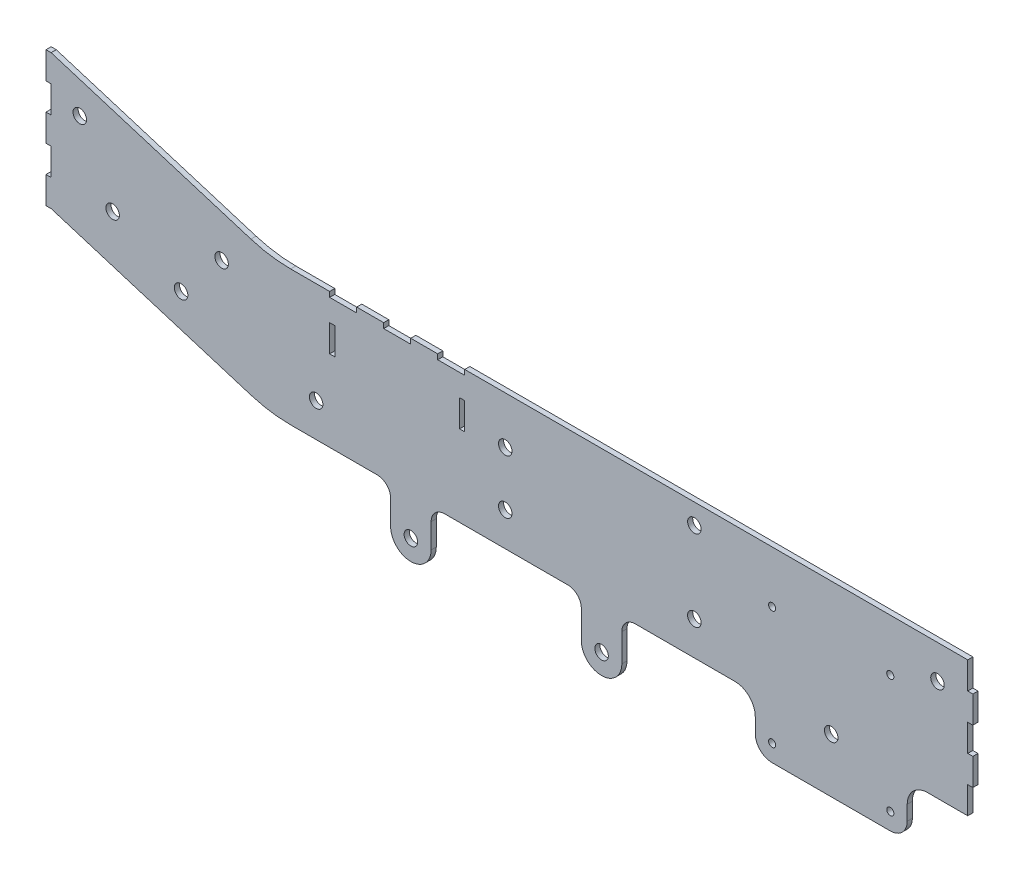
SolidWorks part; units mm, degrees
material "1060 Alloy"
ref_plane "Front Plane" through (0, 0, 0) normal (0, 0, 1) x (1, 0, 0)
ref_plane "Top Plane" through (0, 0, 0) normal (0, 1, 0) x (1, 0, 0)
ref_plane "Right Plane" through (0, 0, 0) normal (1, 0, 0) x (0, 0, -1)
sketch "Sketch2" plane through (0, 0, 0) normal (0, 0, 1) x (1, 0, 0)
  line L41 (-214.6997, -160.1998) -> (-26.8739, -218.0697)
  line L42 (10.5206, -223.6998) -> (91.8093, -223.6998)
  line L43 (104.5093, -236.3998) -> (104.5093, -259.4448)
  line L44 (142.6093, -259.4448) -> (142.6093, -236.3998)
  line L45 (155.3093, -223.6998) -> (271.0993, -223.6998)
  line L46 (283.7993, -236.3998) -> (283.7993, -262.6248)
  line L47 (321.8993, -262.6248) -> (321.8993, -236.3998)
  line L48 (334.5993, -223.6998) -> (476.2017, -223.6998)
  line L49 (561.2969, -223.6998) -> (656.7743, -223.6998)
  line L50 (656.7743, -223.6998) -> (656.7743, -198.2998)
  line L51 (656.7743, -198.2998) -> (651.9483, -198.2998)
  line L52 (651.9483, -198.2998) -> (651.9483, -172.8998)
  line L53 (651.9483, -172.8998) -> (656.7743, -172.8998)
  line L54 (656.7743, -172.8998) -> (656.7743, -147.4998)
  line L55 (656.7743, -147.4998) -> (651.9483, -147.4998)
  line L56 (651.9483, -147.4998) -> (651.9483, -122.0998)
  line L57 (651.9483, -122.0998) -> (656.7743, -122.0998)
  line L58 (656.7743, -122.0998) -> (656.7743, -96.6998)
  line L59 (656.7743, -96.6998) -> (174.1743, -96.6998)
  line L60 (174.1743, -96.6998) -> (174.1743, -101.5258)
  line L61 (174.1743, -101.5258) -> (148.7743, -101.5258)
  line L62 (148.7743, -101.5258) -> (148.7743, -96.6998)
  line L63 (148.7743, -96.6998) -> (123.3743, -96.6998)
  line L64 (123.3743, -96.6998) -> (123.3743, -101.5258)
  line L65 (123.3743, -101.5258) -> (97.9743, -101.5258)
  line L66 (97.9743, -101.5258) -> (97.9743, -96.6998)
  line L67 (97.9743, -96.6998) -> (72.5743, -96.6998)
  line L68 (72.5743, -96.6998) -> (72.5743, -101.5258)
  line L69 (72.5743, -101.5258) -> (47.1743, -101.5258)
  line L70 (47.1743, -101.5258) -> (47.1743, -96.6998)
  line L71 (47.1743, -96.6998) -> (10.5206, -96.6998)
  line L72 (-214.6997, -160.1998) -> (-26.8739, -218.0697)
  line L73 (-219.5257, -33.1998) -> (-219.5257, -58.5998)
  line L74 (-219.5257, -58.5998) -> (-214.6997, -58.5998)
  line L75 (-214.6997, -58.5998) -> (-214.6997, -83.9998)
  line L76 (-214.6997, -83.9998) -> (-219.5257, -83.9998)
  line L77 (-219.5257, -83.9998) -> (-219.5257, -109.3998)
  line L78 (-219.5257, -109.3998) -> (-214.6997, -109.3998)
  line L79 (-214.6997, -109.3998) -> (-214.6997, -134.7998)
  line L80 (-214.6997, -134.7998) -> (-219.5257, -134.7998)
  line L81 (-219.5257, -134.7998) -> (-219.5257, -160.1998)
  line L82 (-26.8739, -91.0697) -> (-214.6997, -33.1998)
  line L83 (10.5206, -223.6998) -> (91.8093, -223.6998)
  line L84 (104.5093, -236.3998) -> (104.5093, -259.4448)
  line L85 (142.6093, -259.4448) -> (142.6093, -236.3998)
  line L86 (155.3093, -223.6998) -> (271.0993, -223.6998)
  line L87 (283.7993, -236.3998) -> (283.7993, -262.6248)
  line L88 (321.8993, -262.6248) -> (321.8993, -236.3998)
  line L89 (334.5993, -223.6998) -> (476.2017, -223.6998)
  line L90 (561.2969, -223.6998) -> (656.7743, -223.6998)
  line L91 (656.7743, -223.6998) -> (656.7743, -198.2998)
  line L92 (656.7743, -198.2998) -> (651.9483, -198.2998)
  line L93 (651.9483, -198.2998) -> (651.9483, -172.8998)
  line L94 (651.9483, -172.8998) -> (656.7743, -172.8998)
  line L95 (656.7743, -172.8998) -> (656.7743, -147.4998)
  line L96 (656.7743, -147.4998) -> (651.9483, -147.4998)
  line L97 (651.9483, -147.4998) -> (651.9483, -122.0998)
  line L98 (651.9483, -122.0998) -> (656.7743, -122.0998)
  line L99 (656.7743, -122.0998) -> (656.7743, -96.6998)
  line L100 (656.7743, -96.6998) -> (174.1743, -96.6998)
  line L101 (174.1743, -96.6998) -> (174.1743, -101.5258)
  line L102 (174.1743, -101.5258) -> (148.7743, -101.5258)
  line L103 (148.7743, -101.5258) -> (148.7743, -96.6998)
  line L104 (148.7743, -96.6998) -> (123.3743, -96.6998)
  line L105 (123.3743, -96.6998) -> (123.3743, -101.5258)
  line L106 (123.3743, -101.5258) -> (97.9743, -101.5258)
  line L107 (97.9743, -101.5258) -> (97.9743, -96.6998)
  line L108 (97.9743, -96.6998) -> (72.5743, -96.6998)
  line L109 (72.5743, -96.6998) -> (72.5743, -101.5258)
  line L110 (72.5743, -101.5258) -> (47.1743, -101.5258)
  line L111 (47.1743, -101.5258) -> (47.1743, -96.6998)
  line L112 (47.1743, -96.6998) -> (10.5206, -96.6998)
  line L113 (-26.8739, -91.0697) -> (-214.6997, -33.1998)
  line L114 (-219.5257, -33.1998) -> (-219.5257, -58.5998)
  line L115 (-219.5257, -58.5998) -> (-214.6997, -58.5998)
  line L116 (-214.6997, -58.5998) -> (-214.6997, -83.9998)
  line L117 (-214.6997, -83.9998) -> (-219.5257, -83.9998)
  line L118 (-219.5257, -83.9998) -> (-219.5257, -109.3998)
  line L119 (-219.5257, -109.3998) -> (-214.6997, -109.3998)
  line L120 (-214.6997, -109.3998) -> (-214.6997, -134.7998)
  line L121 (-214.6997, -134.7998) -> (-219.5257, -134.7998)
  line L122 (-219.5257, -134.7998) -> (-219.5257, -160.1998)
  line L412 (-214.6997, -33.1998) -> (-219.5257, -33.1998)
  line L413 (-214.6997, -33.1998) -> (-219.5257, -33.1998)
  line L414 (-219.5257, -160.1998) -> (-214.6997, -160.1998)
  line L415 (-219.5257, -160.1998) -> (-214.6997, -160.1998)
  arc A11 (-26.8739, -218.0697) -> (10.5206, -223.6998) centre (10.5206, -96.6998) ccw
  arc A12 (104.5093, -236.3998) -> (91.8093, -223.6998) centre (91.8093, -236.3998) ccw
  arc A13 (104.5093, -259.4448) -> (142.6093, -259.4448) centre (123.5593, -259.4448) ccw
  arc A14 (155.3093, -223.6998) -> (142.6093, -236.3998) centre (155.3093, -236.3998) ccw
  arc A15 (283.7993, -236.3998) -> (271.0993, -223.6998) centre (271.0993, -236.3998) ccw
  arc A16 (283.7993, -262.6248) -> (321.8993, -262.6248) centre (302.8493, -262.6248) ccw
  arc A17 (334.5993, -223.6998) -> (321.8993, -236.3998) centre (334.5993, -236.3998) ccw
  arc A18 (486.8386, -229.461) -> (476.2017, -223.6998) centre (476.2017, -236.3998) ccw
  arc A19 (486.8386, -229.461) -> (550.66, -229.461) centre (518.7493, -208.6448) ccw
  arc A20 (561.2969, -223.6998) -> (550.66, -229.461) centre (561.2969, -236.3998) ccw
  arc A21 (-26.8739, -218.0697) -> (10.5206, -223.6998) centre (10.5206, -96.6998) ccw
  arc A22 (-26.8739, -91.0697) -> (10.5206, -96.6998) centre (10.5206, 30.3002) ccw
  arc A23 (104.5093, -236.3998) -> (91.8093, -223.6998) centre (91.8093, -236.3998) ccw
  arc A24 (104.5093, -259.4448) -> (142.6093, -259.4448) centre (123.5593, -259.4448) ccw
  arc A25 (155.3093, -223.6998) -> (142.6093, -236.3998) centre (155.3093, -236.3998) ccw
  arc A26 (283.7993, -236.3998) -> (271.0993, -223.6998) centre (271.0993, -236.3998) ccw
  arc A27 (283.7993, -262.6248) -> (321.8993, -262.6248) centre (302.8493, -262.6248) ccw
  arc A28 (334.5993, -223.6998) -> (321.8993, -236.3998) centre (334.5993, -236.3998) ccw
  arc A29 (486.8386, -229.461) -> (476.2017, -223.6998) centre (476.2017, -236.3998) ccw
  arc A30 (486.8386, -229.461) -> (550.66, -229.461) centre (518.7493, -208.6448) ccw
  arc A31 (561.2969, -223.6998) -> (550.66, -229.461) centre (561.2969, -236.3998) ccw
  arc A32 (-26.8739, -91.0697) -> (10.5206, -96.6998) centre (10.5206, 30.3002) ccw
  circle A56 centre (390.0743, -191.9498) radius 6.35
  circle A57 centre (390.0743, -191.9498) radius 6.35
  circle A58 centre (390.0743, -115.7498) radius 6.35
  circle A59 centre (390.0743, -115.7498) radius 6.35
  circle A60 centre (518.7493, -221.3448) radius 6.35
  circle A61 centre (518.7493, -221.3448) radius 6.35
  circle A62 centre (618.6743, -128.4498) radius 6.35
  circle A63 centre (618.6743, -128.4498) radius 6.35
  circle A64 centre (302.8493, -262.6248) radius 6.35
  circle A65 centre (302.8493, -262.6248) radius 6.35
  circle A66 centre (212.2743, -191.9498) radius 6.35
  circle A67 centre (212.2743, -191.9498) radius 6.35
  circle A68 centre (212.2743, -141.1498) radius 6.35
  circle A69 centre (212.2743, -141.1498) radius 6.35
  circle A70 centre (123.5593, -259.4448) radius 6.35
  circle A71 centre (123.5593, -259.4448) radius 6.35
  circle A72 centre (34.4743, -191.9498) radius 6.35
  circle A73 centre (34.4743, -191.9498) radius 6.35
  circle A74 centre (-92.5257, -166.5498) radius 6.35
  circle A75 centre (-92.5257, -166.5498) radius 6.35
  circle A76 centre (-156.8507, -133.7248) radius 6.35
  circle A77 centre (-156.8507, -133.7248) radius 6.35
  circle A78 centre (-54.4257, -122.0998) radius 6.35
  circle A79 centre (-54.4257, -122.0998) radius 6.35
  circle A80 centre (-187.7757, -71.2998) radius 6.35
  circle A81 centre (-187.7757, -71.2998) radius 6.35
  dimension "D1" = 0
  dimension "D2" = 0
  dimension "D3" = 0
  dimension "D4" = 0
  dimension "D5" = 0
  dimension "D6" = 0
  dimension "D7" = 0
  dimension "D8" = 0
  dimension "D9" = 0
  dimension "D10" = 0
  dimension "D11" = 0
  dimension "D12" = 0
  dimension "D13" = 0
  dimension "D14" = 0
extrude "base" add sketch "Sketch2" along normal blind 4.826
sketch "Sketch3" plane through (0, 0, 4.826) normal (0, 0, 1) x (1, 0, 0)
  line L0 (47.1743, -101.5258) -> (47.1743, -96.6998) construction
  line L1 (169.3483, -122.0998) -> (174.1743, -122.0998)
  line L2 (169.3483, -122.0998) -> (169.3483, -147.4998)
  line L3 (169.3483, -147.4998) -> (174.1743, -147.4998)
  line L4 (174.1743, -122.0998) -> (174.1743, -147.4998)
  line L5 (47.1743, -122.0998) -> (52.0003, -122.0998)
  line L6 (47.1743, -122.0998) -> (47.1743, -147.4998)
  line L7 (47.1743, -147.4998) -> (52.0003, -147.4998)
  line L8 (52.0003, -122.0998) -> (52.0003, -147.4998)
  line L9 (174.1743, -96.6998) -> (174.1743, -101.5258) construction
  line L10 (97.9743, -96.6998) -> (72.5743, -96.6998) construction
  dimension "D1" = 4.826
  dimension "D2" = 25.4
  dimension "D3" = 25.4
extrude "center support vertical holes" cut sketch "Sketch3" against normal through all
sketch "Sketch4" plane through (656.7743, 0, 0) normal (1, 0, 0) x (0, 0, -1)
  line L0 (0, -122.0998) -> (0, -96.6998) construction
  line L1 (0, -96.6998) -> (-4.826, -96.6998) construction
  line L2 (-4.826, -96.6998) -> (-4.826, -122.0998) construction
  line L3 (-4.826, -122.0998) -> (0, -122.0998) construction
  line L4 (0, -172.8998) -> (0, -147.4998) construction
  line L5 (0, -147.4998) -> (-4.826, -147.4998) construction
  line L6 (-4.826, -147.4998) -> (-4.826, -172.8998) construction
  line L7 (-4.826, -172.8998) -> (0, -172.8998) construction
  line L8 (0, -223.6998) -> (0, -198.2998) construction
  line L9 (0, -198.2998) -> (-4.826, -198.2998) construction
  line L10 (-4.826, -198.2998) -> (-4.826, -223.6998) construction
  line L11 (-4.826, -223.6998) -> (0, -223.6998) construction
  line L12 (0, -122.0998) -> (0, -96.6998)
  line L13 (0, -96.6998) -> (-4.826, -96.6998)
  line L14 (-4.826, -96.6998) -> (-4.826, -122.0998)
  line L15 (-4.826, -122.0998) -> (0, -122.0998)
  line L16 (0, -172.8998) -> (0, -147.4998)
  line L17 (0, -147.4998) -> (-4.826, -147.4998)
  line L18 (-4.826, -147.4998) -> (-4.826, -172.8998)
  line L19 (-4.826, -172.8998) -> (0, -172.8998)
  line L20 (0, -223.6998) -> (0, -198.2998)
  line L21 (0, -198.2998) -> (-4.826, -198.2998)
  line L22 (-4.826, -198.2998) -> (-4.826, -223.6998)
  line L23 (-4.826, -223.6998) -> (0, -223.6998)
extrude "Cut-Extrude2" cut sketch "Sketch4" against normal blind 9.652
sketch "Sketch5" plane through (0, 0, 0) normal (0, 0, 1) x (1, 0, 0)
  line L0 (463.2122, -272.4369) -> (574.3372, -272.4369)
  line L1 (447.3372, -256.5619) -> (447.3372, -242.7498)
  line L3 (590.2122, -256.5619) -> (590.2122, -242.7498)
  line L43 (647.1223, -198.2998) -> (651.9483, -198.2998)
  line L44 (651.9483, -198.2998) -> (651.9483, -172.8998)
  line L45 (651.9483, -172.8998) -> (647.1223, -172.8998)
  line L46 (647.1223, -172.8998) -> (647.1223, -147.4998)
  line L47 (647.1223, -147.4998) -> (651.9483, -147.4998)
  line L48 (651.9483, -147.4998) -> (651.9483, -122.0998)
  line L49 (651.9483, -122.0998) -> (647.1223, -122.0998)
  line L50 (647.1223, -122.0998) -> (647.1223, -96.6998)
  line L51 (647.1223, -96.6998) -> (174.1743, -96.6998)
  line L52 (174.1743, -96.6998) -> (174.1743, -101.5258)
  line L53 (174.1743, -101.5258) -> (148.7743, -101.5258)
  line L54 (148.7743, -101.5258) -> (148.7743, -96.6998)
  line L55 (148.7743, -96.6998) -> (123.3743, -96.6998)
  line L56 (123.3743, -96.6998) -> (123.3743, -101.5258)
  line L57 (123.3743, -101.5258) -> (97.9743, -101.5258)
  line L58 (97.9743, -101.5258) -> (97.9743, -96.6998)
  line L59 (97.9743, -96.6998) -> (72.5743, -96.6998)
  line L60 (72.5743, -96.6998) -> (72.5743, -101.5258)
  line L61 (72.5743, -101.5258) -> (47.1743, -101.5258)
  line L62 (47.1743, -101.5258) -> (47.1743, -96.6998)
  line L63 (47.1743, -96.6998) -> (10.5206, -96.6998)
  line L64 (-26.8739, -91.0697) -> (-214.6997, -33.1998)
  line L65 (-214.6997, -33.1998) -> (-219.5257, -33.1998)
  line L66 (-219.5257, -33.1998) -> (-219.5257, -58.5998)
  line L67 (-219.5257, -58.5998) -> (-214.6997, -58.5998)
  line L68 (-214.6997, -58.5998) -> (-214.6997, -83.9998)
  line L69 (-214.6997, -83.9998) -> (-219.5257, -83.9998)
  line L70 (-219.5257, -83.9998) -> (-219.5257, -109.3998)
  line L71 (-219.5257, -109.3998) -> (-214.6997, -109.3998)
  line L72 (-214.6997, -109.3998) -> (-214.6997, -134.7998)
  line L73 (-214.6997, -134.7998) -> (-219.5257, -134.7998)
  line L74 (-219.5257, -134.7998) -> (-219.5257, -160.1998)
  line L75 (-219.5257, -160.1998) -> (-214.6997, -160.1998)
  line L76 (-214.6997, -160.1998) -> (-26.8739, -218.0697)
  line L77 (10.5206, -223.6998) -> (91.8093, -223.6998)
  line L78 (104.5093, -236.3998) -> (104.5093, -259.4448)
  line L79 (142.6093, -259.4448) -> (142.6093, -236.3998)
  line L80 (155.3093, -223.6998) -> (271.0993, -223.6998)
  line L81 (283.7993, -236.3998) -> (283.7993, -262.6248)
  line L82 (321.8993, -262.6248) -> (321.8993, -236.3998)
  line L83 (334.5993, -223.6998) -> (476.2017, -223.6998)
  line L84 (561.2969, -223.6998) -> (647.1223, -223.6998)
  line L85 (647.1223, -223.6998) -> (647.1223, -198.2998)
  line L86 (647.1223, -198.2998) -> (651.9483, -198.2998)
  line L87 (651.9483, -198.2998) -> (651.9483, -172.8998)
  line L88 (651.9483, -172.8998) -> (647.1223, -172.8998)
  line L89 (647.1223, -172.8998) -> (647.1223, -147.4998)
  line L90 (647.1223, -147.4998) -> (651.9483, -147.4998)
  line L91 (651.9483, -147.4998) -> (651.9483, -122.0998)
  line L92 (651.9483, -122.0998) -> (647.1223, -122.0998)
  line L93 (647.1223, -122.0998) -> (647.1223, -96.6998)
  line L94 (647.1223, -96.6998) -> (174.1743, -96.6998)
  line L95 (174.1743, -96.6998) -> (174.1743, -101.5258)
  line L96 (174.1743, -101.5258) -> (148.7743, -101.5258)
  line L97 (148.7743, -101.5258) -> (148.7743, -96.6998)
  line L98 (148.7743, -96.6998) -> (123.3743, -96.6998)
  line L99 (123.3743, -96.6998) -> (123.3743, -101.5258)
  line L100 (123.3743, -101.5258) -> (97.9743, -101.5258)
  line L101 (97.9743, -101.5258) -> (97.9743, -96.6998)
  line L102 (97.9743, -96.6998) -> (72.5743, -96.6998)
  line L103 (72.5743, -96.6998) -> (72.5743, -101.5258)
  line L104 (72.5743, -101.5258) -> (47.1743, -101.5258)
  line L105 (47.1743, -101.5258) -> (47.1743, -96.6998)
  line L106 (47.1743, -96.6998) -> (10.5206, -96.6998)
  line L107 (-26.8739, -91.0697) -> (-214.6997, -33.1998)
  line L108 (-214.6997, -33.1998) -> (-219.5257, -33.1998)
  line L109 (-219.5257, -33.1998) -> (-219.5257, -58.5998)
  line L110 (-219.5257, -58.5998) -> (-214.6997, -58.5998)
  line L111 (-214.6997, -58.5998) -> (-214.6997, -83.9998)
  line L112 (-214.6997, -83.9998) -> (-219.5257, -83.9998)
  line L113 (-219.5257, -83.9998) -> (-219.5257, -109.3998)
  line L114 (-219.5257, -109.3998) -> (-214.6997, -109.3998)
  line L115 (-214.6997, -109.3998) -> (-214.6997, -134.7998)
  line L116 (-214.6997, -134.7998) -> (-219.5257, -134.7998)
  line L117 (-219.5257, -134.7998) -> (-219.5257, -160.1998)
  line L118 (-219.5257, -160.1998) -> (-214.6997, -160.1998)
  line L119 (-214.6997, -160.1998) -> (-26.8739, -218.0697)
  line L120 (10.5206, -223.6998) -> (91.8093, -223.6998)
  line L121 (104.5093, -236.3998) -> (104.5093, -259.4448)
  line L122 (142.6093, -259.4448) -> (142.6093, -236.3998)
  line L123 (155.3093, -223.6998) -> (271.0993, -223.6998)
  line L124 (283.7993, -236.3998) -> (283.7993, -262.6248)
  line L125 (321.8993, -262.6248) -> (321.8993, -236.3998)
  line L126 (334.5993, -223.6998) -> (476.2017, -223.6998)
  line L127 (561.2969, -223.6998) -> (647.1223, -223.6998)
  line L128 (647.1223, -223.6998) -> (647.1223, -198.2998)
  circle A0 centre (574.3372, -256.5619) radius 3.3528 construction
  circle A1 centre (463.2122, -256.5619) radius 3.3528 construction
  circle A2 centre (463.2122, -145.4369) radius 3.3528 construction
  circle A3 centre (574.3372, -145.4369) radius 3.2512 construction
  circle A4 centre (574.3372, -256.5619) radius 3.3528
  circle A5 centre (463.2122, -256.5619) radius 3.3528
  circle A6 centre (463.2122, -145.4369) radius 3.3528
  circle A7 centre (574.3372, -145.4369) radius 3.2512
  arc A8 (447.3372, -256.5619) -> (463.2122, -272.4369) centre (463.2122, -256.5619) ccw
  arc A9 (574.3372, -272.4369) -> (590.2122, -256.5619) centre (574.3372, -256.5619) ccw
  arc A10 (447.3372, -242.7498) -> (428.2872, -223.6998) centre (428.2872, -242.7498) ccw
  arc A11 (609.2622, -223.6998) -> (590.2122, -242.7498) centre (609.2622, -242.7498) ccw
  arc A21 (-26.8739, -91.0697) -> (10.5206, -96.6998) centre (10.5206, 30.3002) ccw
  arc A22 (-26.8739, -218.0697) -> (10.5206, -223.6998) centre (10.5206, -96.6998) ccw
  arc A23 (104.5093, -236.3998) -> (91.8093, -223.6998) centre (91.8093, -236.3998) ccw
  arc A24 (104.5093, -259.4448) -> (142.6093, -259.4448) centre (123.5593, -259.4448) ccw
  arc A25 (155.3093, -223.6998) -> (142.6093, -236.3998) centre (155.3093, -236.3998) ccw
  arc A26 (283.7993, -236.3998) -> (271.0993, -223.6998) centre (271.0993, -236.3998) ccw
  arc A27 (283.7993, -262.6248) -> (321.8993, -262.6248) centre (302.8493, -262.6248) ccw
  arc A28 (334.5993, -223.6998) -> (321.8993, -236.3998) centre (334.5993, -236.3998) ccw
  arc A29 (486.8386, -229.461) -> (476.2017, -223.6998) centre (476.2017, -236.3998) ccw
  arc A30 (486.8386, -229.461) -> (550.66, -229.461) centre (518.7493, -208.6448) ccw
  arc A31 (561.2969, -223.6998) -> (550.66, -229.461) centre (561.2969, -236.3998) ccw
  arc A32 (-26.8739, -91.0697) -> (10.5206, -96.6998) centre (10.5206, 30.3002) ccw
  arc A33 (-26.8739, -218.0697) -> (10.5206, -223.6998) centre (10.5206, -96.6998) ccw
  arc A34 (104.5093, -236.3998) -> (91.8093, -223.6998) centre (91.8093, -236.3998) ccw
  arc A35 (104.5093, -259.4448) -> (142.6093, -259.4448) centre (123.5593, -259.4448) ccw
  arc A36 (155.3093, -223.6998) -> (142.6093, -236.3998) centre (155.3093, -236.3998) ccw
  arc A37 (283.7993, -236.3998) -> (271.0993, -223.6998) centre (271.0993, -236.3998) ccw
  arc A38 (283.7993, -262.6248) -> (321.8993, -262.6248) centre (302.8493, -262.6248) ccw
  arc A39 (334.5993, -223.6998) -> (321.8993, -236.3998) centre (334.5993, -236.3998) ccw
  arc A40 (486.8386, -229.461) -> (476.2017, -223.6998) centre (476.2017, -236.3998) ccw
  arc A41 (486.8386, -229.461) -> (550.66, -229.461) centre (518.7493, -208.6448) ccw
  arc A42 (561.2969, -223.6998) -> (550.66, -229.461) centre (561.2969, -236.3998) ccw
  arc M56 (455.2747, -263.7056) -> (456.0685, -264.4994) centre (456.0685, -263.7056) ccw
  line M57 (456.0685, -264.4994) -> (581.481, -264.4994)
  arc M58 (581.481, -264.4994) -> (582.2747, -263.7056) centre (581.481, -263.7056) ccw
  line M59 (582.2747, -263.7056) -> (582.2747, -138.2931)
  line M63 (455.2747, -138.2931) -> (455.2747, -263.7056)
  circle M64 centre (480.5665, -220.0494) radius 5.5626
  circle M68 centre (463.2122, -256.5619) radius 3.3528
  circle M70 centre (574.3372, -256.5619) radius 3.3528
  circle M74 centre (556.9829, -220.0494) radius 5.5626
  dimension "D2" = 31.75
  dimension "D3" = 19.05
  dimension "D1" = 0
extrude "Boss-Extrude1" add sketch "Sketch5" along normal through all contours A11 L127 L126 A10 L1 A8 L0 A9 L3 M59 M58 M57 M56 M63 | L127 A42 A41 A40 L126 M74 M64 M63 M56 M57 M58 M59 M70 M68 | A40 M64 | A42 M74 region at (453.3122, -266.4619, 0) region at (518.7816, -247.2481, 0) region at (479.3181, -224.7256, 0) region at (558.2159, -224.7224, 0)
sketch "Sketch6" plane through (0, 0, 4.826) normal (0, 0, 1) x (1, 0, 0)
  circle A0 centre (463.1868, -145.4369) radius 3.3528 construction
  circle A2 centre (463.1868, -145.4369) radius 3.3528
  circle A3 centre (574.3118, -145.4369) radius 3.3528 construction
  circle A4 centre (574.3118, -145.4369) radius 3.3528
extrude "Cut-Extrude3" cut sketch "Sketch6" against normal through all
equation "\"sheet width\"= .19"
equation "\"width\"= 24.5"
equation "\"length\"= 34.5"
equation "\"standoff hole size\"= .5"
equation "\"ground clearence\"= 3"
equation "\"small drive pulley\"= 74.55mm"
equation "\"large drive pulley\"= 150.95mm"
equation "\"drive axle hole size\"= .5"
equation "\"front pulley clearence\"= 1"
equation "\"center support location\"= 19"
equation "\"D1@Sketch3\"=\"sheet width\""
equation "\"D1@base\"=\"sheet width\""
equation "\"D1@Cut-Extrude2\"=\"sheet width\"*2"
